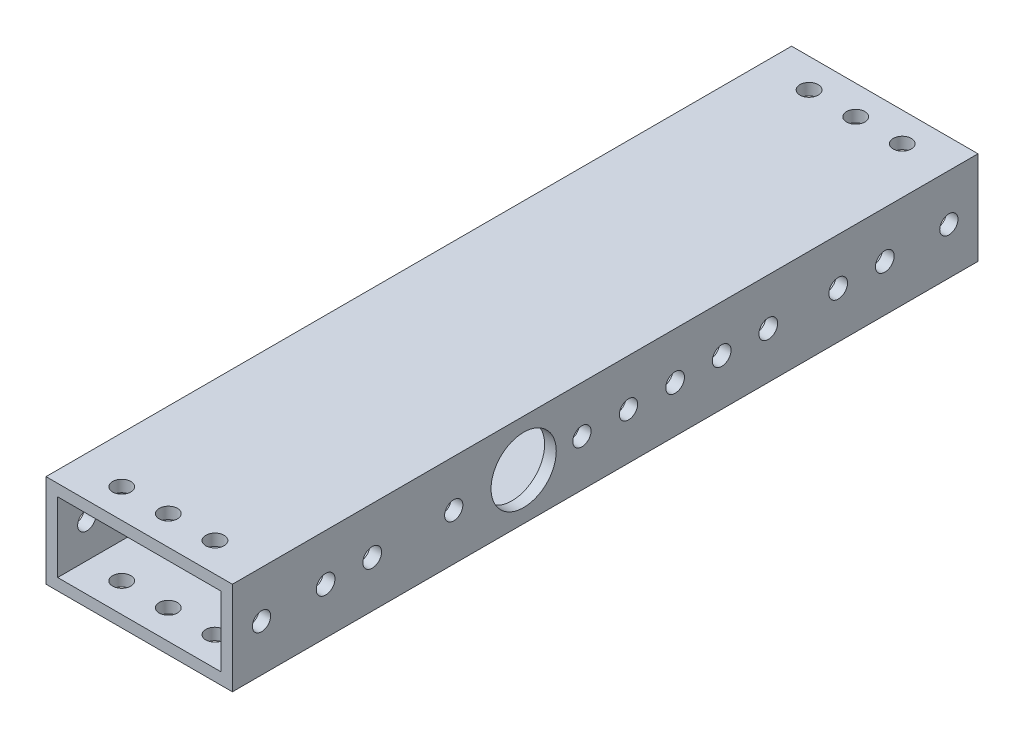
SolidWorks part; units mm, degrees
material "6061-T6 (SS)"
ref_plane "Front Plane" through (0, 0, 0) normal (0, 0, 1) x (1, 0, 0)
ref_plane "Top Plane" through (0, 0, 0) normal (0, 1, 0) x (1, 0, 0)
ref_plane "Right Plane" through (0, 0, 0) normal (1, 0, 0) x (0, 0, -1)
sketch "Sketch1" plane through (0, 0, 0) normal (0, 0, 1) x (1, 0, 0)
  line L0 (-22.225, 9.525) -> (22.225, 9.525)
  line L1 (-25.4, -12.7) -> (25.4, -12.7)
  line L2 (-25.4, -12.7) -> (-25.4, 12.7)
  line L3 (-25.4, 12.7) -> (25.4, 12.7)
  line L4 (25.4, -12.7) -> (25.4, 12.7)
  line L5 (-25.4, -12.7) -> (25.4, 12.7) construction
  line L6 (-25.4, 12.7) -> (25.4, -12.7) construction
  line L7 (22.225, -9.525) -> (22.225, 9.525)
  line L8 (-22.225, -9.525) -> (22.225, -9.525)
  line L9 (-22.225, -9.525) -> (-22.225, 9.525)
  point P0 (0, 0)
  dimension "D1" = 50.8
  dimension "D2" = 25.4
  dimension "D3" = 3.175
extrude "Boss-Extrude1" add sketch "Sketch1" along normal mid plane 203.2
sketch "Sketch3" plane through (0, 12.7, 0) normal (0, 1, 0) x (1, 0, 0)
  line L0 (-25.4, 0) -> (25.4, 0) construction
  line L1 (-25.4, -101.6) -> (-25.4, 101.6) construction
  line L2 (25.4, -101.6) -> (25.4, 101.6) construction
  line L3 (25.4, -101.6) -> (-25.4, -101.6) construction
  circle A0 centre (-12.7, -93.6625) radius 2.4892
  circle A1 centre (0, -93.6625) radius 2.4892
  circle A2 centre (12.7, -93.6625) radius 2.4892
  circle A3 centre (12.7, 93.6625) radius 2.4892
  circle A4 centre (0, 93.6625) radius 2.4892
  circle A5 centre (-12.7, 93.6625) radius 2.4892
  dimension "D1" = 4.9784
  dimension "D2" = 12.7
  dimension "D3" = 12.7
  dimension "D4" = 7.9375
extrude "Cut-Extrude2" cut sketch "Sketch3" against normal through all
sketch "Sketch4" plane through (25.4, 0, 0) normal (1, 0, 0) x (0, 0, -1)
  line L0 (-22.225, 0) -> (-45.1908, 0) construction
  line L1 (-13.335, 0) -> (-31.115, 0) construction
  line L8 (-22.225, 0) -> (31.75, 0) construction
  line L9 (0, 12.7) -> (0, -12.7) construction
  line L10 (-101.6, 12.7) -> (101.6, 12.7) construction
  line L11 (-101.6, -12.7) -> (101.6, -12.7) construction
  circle A0 centre (-22.225, 0) radius 8.89
  circle A9 centre (31.75, 0) radius 2.5527
  circle A10 centre (19.05, 0) radius 2.5527
  dimension "D2" = 17.78
  dimension "D3" = 22.225
  dimension "D1" = 53.975
  dimension "D4" = 5.1054
  dimension "D6" = 41.275
extrude "Cut-Extrude3" cut sketch "Sketch4" against normal through all contours A0 | A9 | A10
sketch "Sketch2" plane through (25.4, 0, 0) normal (1, 0, 0) x (0, 0, -1)
  line L0 (-101.6, -12.7) -> (-101.6, 12.7) construction
  line L1 (0, 12.7) -> (0, -12.7) construction
  line L2 (-101.6, 12.7) -> (101.6, 12.7) construction
  line L3 (-101.6, -12.7) -> (101.6, -12.7) construction
  circle A0 centre (-93.6625, 0) radius 2.4892
  circle A1 centre (93.6625, 0) radius 2.4892
  circle A2 centre (-76.2, 0) radius 2.5527
  circle A3 centre (-63.5, 0) radius 2.5527
  circle A4 centre (63.5, 0) radius 2.5527
  circle A5 centre (76.2, 0) radius 2.5527
  dimension "D2" = 4.9784
  dimension "D5" = 5.1054
  dimension "D4" = 25.4
  dimension "D1" = 7.9375
  dimension "D3" = 12.7
extrude "Cut-Extrude1" cut sketch "Sketch2" against normal through all
sketch "Sketch5" plane through (0, -12.7, 0) normal (0, -1, 0) x (1, 0, 0)
  line L0 (-25.4, 101.6) -> (-25.4, -101.6) construction
  line L1 (-25.4, 101.6) -> (25.4, 101.6) construction
  line L4 (25.4, 22.225) -> (-25.4, 22.225) construction
  line L5 (25.4, 101.6) -> (25.4, -101.6) construction
  circle A0 centre (-3.175, 66.675) radius 2.4892
  circle A1 centre (-15.875, 66.675) radius 2.4892
  circle A2 centre (-15.875, 53.975) radius 2.4892
  circle A3 centre (-3.175, 53.975) radius 2.4892
  circle A8 centre (-3.175, -9.525) radius 2.4892
  circle A9 centre (-15.875, -9.525) radius 2.4892
  circle A10 centre (-15.875, -22.225) radius 2.4892
  circle A11 centre (-3.175, -22.225) radius 2.4892
  dimension "D3" = 4.9784
  dimension "D4" = 9.525
  dimension "D7" = 12.7
  dimension "D12" = 79.375
  dimension "D5" = 31.75
  dimension "D6" = 12.7
  dimension "D1" = 2
  dimension "D2" = 2
extrude "Cut-Extrude4" cut sketch "Sketch5" against normal up to next
sketch "Sketch7" plane through (25.4, 0, 0) normal (1, 0, 0) x (0, 0, -1)
  circle A0 centre (44.45, 0) radius 2.5527
  circle A1 centre (31.75, 0) radius 2.5527 construction
  circle A5 centre (6.35, 0) radius 2.4892
  circle A6 centre (-6.35, 0) radius 2.4892
  circle A7 centre (-41.275, 0) radius 2.4892
  circle A8 centre (-22.225, 0) radius 8.89 construction
  dimension "D1" = 12.7
  dimension "D2" = 19.05
  dimension "D3" = 15.875
  dimension "D4" = 12.7
  dimension "D5" = 4.9784
extrude "Cut-Extrude5" cut sketch "Sketch7" against normal up to next contours A0 | A7 | A6 | A5
